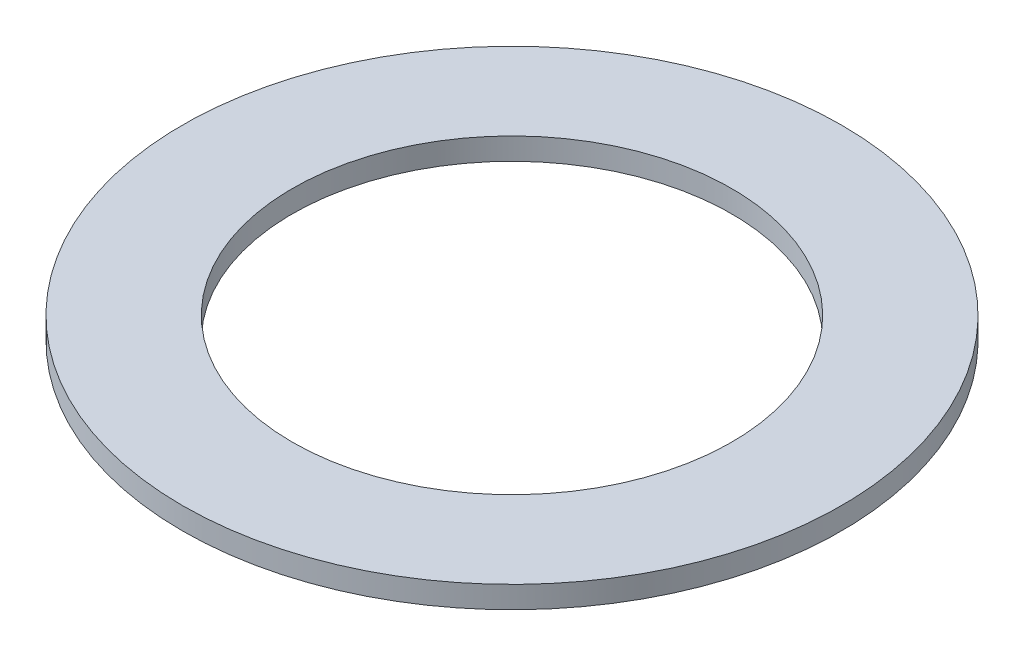
SolidWorks part; units mm, degrees
ref_plane "Front Plane" through (0, 0, 0) normal (0, 0, 1) x (1, 0, 0)
ref_plane "Top Plane" through (0, 0, 0) normal (0, 1, 0) x (1, 0, 0)
ref_plane "Right Plane" through (0, 0, 0) normal (1, 0, 0) x (0, 0, -1)
sketch "Sketch1" plane through (0, 0, 0) normal (0, 1, 0) x (1, 0, 0)
  circle A0 centre (0, 0) radius 75
  dimension "FLANGE_OD" = 150
extrude "Boss-Extrude1" add sketch "Sketch1" along normal blind 5
sketch "Sketch2" plane through (0, 0, 0) normal (0, 1, 0) x (1, 0, 0)
  circle A0 centre (0, 0) radius 50
  dimension "BORE_D" = 100
extrude "Cut-Extrude1" cut sketch "Sketch2" along normal through all
sketch "Sketch3" plane through (0, 5, 0) normal (0, 1, 0) x (1, 0, 0)
  circle A0 centre (0, 0) radius 32.3397 construction
  circle A1 centre (-32.3397, 0) radius 4.1581
  dimension "BOLT_D" = 8.3163
  dimension "BOLT_PCD" = 64.6795
extrude "Cut-Extrude2" cut sketch "Sketch3" against normal blind 3.7742 rebuild error yes
pattern_circular "CirPattern1" count 4 over 360 rebuild error yes
